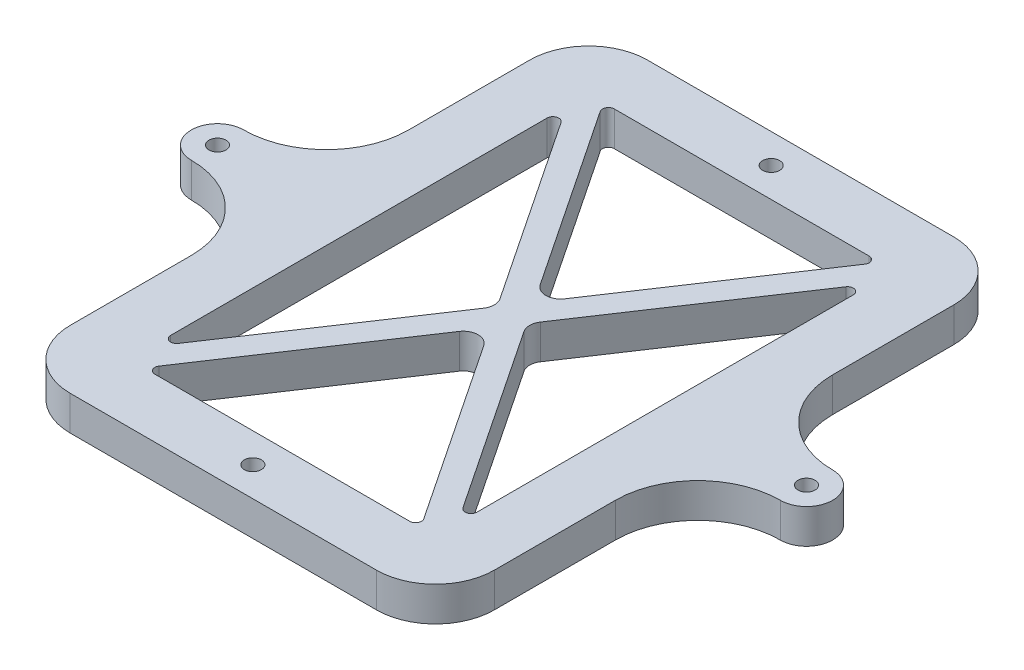
SolidWorks part; units mm, degrees
material "Acrylic (Medium-high impact)"
ref_plane "Front Plane" through (0, 0, 0) normal (0, 0, 1) x (1, 0, 0)
ref_plane "Top Plane" through (0, 0, 0) normal (0, 1, 0) x (1, 0, 0)
ref_plane "Right Plane" through (0, 0, 0) normal (1, 0, 0) x (0, 0, -1)
sketch "Sketch1" plane through (0, 0, 0) normal (0, 1, 0) x (1, 0, 0)
  line L0 (-36, 49) -> (-36, 18.45) construction
  line L1 (-36, 49) -> (36, 49) construction
  line L2 (-36, -49) -> (36, -49) construction
  line L3 (36, 49) -> (36, 18.45) construction
  line L4 (-28.5, -39) -> (-23.5, -39)
  line L5 (-28.5, -39) -> (23.5, 39)
  line L6 (-55, 0) -> (55, 0) construction
  line L7 (-74.55, 39) -> (-36, 39) construction
  line L8 (-26, 39) -> (26, 39)
  line L9 (-26, 39) -> (-26, -39)
  line L10 (-26, -39) -> (26, -39)
  line L11 (26, 39) -> (26, -39)
  line L12 (-26, 39) -> (26, -39) construction
  line L13 (-26, -39) -> (26, 39) construction
  line L14 (-71.5261, -39) -> (60.5097, -39) construction
  line L15 (-36, 39) -> (-36, 18.45)
  line L16 (-26, -996.6512) -> (-26, 49003.3488) construction
  line L17 (26, -1000) -> (26, 49000) construction
  line L18 (-26, 49) -> (26, 49)
  line L19 (36, 39) -> (36, 18.45)
  line L20 (-26, -49) -> (26, -49)
  line L21 (-62.4665, 0) -> (49937.5335, 0) construction
  line L22 (0, 0) -> (0, 50000) construction
  line L23 (-23.5, -39) -> (26, 35.25)
  line L24 (23.5, 39) -> (26, 39)
  line L25 (28.5, -39) -> (23.5, -39)
  line L26 (28.5, -39) -> (-23.5, 39)
  line L27 (23.5, -39) -> (-26, 35.25)
  line L28 (-23.5, 39) -> (-26, 39)
  line L29 (-36, -18.45) -> (-36, -49) construction
  line L30 (-36, -18.45) -> (-36, -39)
  line L31 (36, -18.45) -> (36, -49) construction
  line L32 (36, -18.45) -> (36, -39)
  line L33 (-26, 39) -> (26, 39) construction
  line L34 (36, 39) -> (60.5097, 39) construction
  arc A0 (-36, 39) -> (-26, 49) centre (-26, 39) cw
  arc A1 (26, 49) -> (36, 39) centre (26, 39) cw
  arc A2 (36, -39) -> (26, -49) centre (26, -39) cw
  arc A3 (-26, -49) -> (-36, -39) centre (-26, -39) cw
  circle A4 centre (0, 44) radius 1.45
  circle A5 centre (0, -44) radius 1.45
  circle A6 centre (-50, 0) radius 1.45
  circle A7 centre (50, 0) radius 1.45
  arc A8 (-50, -4.45) -> (-50, 4.45) centre (-50, 0) cw
  arc A9 (-50, 4.45) -> (-36, 18.45) centre (-50, 18.45) ccw
  arc A10 (-50, -4.45) -> (-36, -18.45) centre (-50, -18.45) cw
  arc A11 (50, -4.45) -> (50, 4.45) centre (50, 0) ccw
  arc A12 (50, -4.45) -> (36, -18.45) centre (50, -18.45) ccw
  arc A13 (50, 4.45) -> (36, 18.45) centre (50, 18.45) cw
  point P1 (0, 0)
  point P3 (0, 0)
  point P24 (26, 0)
  point P25 (36, 39)
  point P26 (36, -39)
  point P27 (-26, 49)
  point P28 (26, 49)
  point P34 (26, -49)
  point P35 (-26, -49)
  dimension "D7" = 2.9
  dimension "D8" = 2.5
  dimension "D10" = 50
  dimension "D11" = 2.9
  dimension "D5" = 44
  dimension "D9" = 3
  dimension "D1" = 98
  dimension "D2" = 72
  dimension "D3" = 78
  dimension "D4" = 52
extrude "Boss-Extrude1" add sketch "Sketch1" along normal blind 5.85 contours A3 L20 A2 L19 A1 L18 A0 L15 A7 A6 A5 A4 L28 L8 L24 L23 L11 L26 L25 L10 L4 L5 L9 L27 | L23 L27 L5 L9 L4 | L27 L5 L26 L8 L9 | L9 L28 L27 | L9 L5 L4 | L25 L26 L11 | L27 L10 L11 L26 L23 | L27 L23 L26 L5 | L26 L23 L11 L8 L5 | L24 L11 L23 region at (-26.8333, 0, 37.75) region at (-13.3152, 0, 19.9728) region at (-13.3152, 0, -19.9728) region at (0, 0, 0) region at (13.3152, 0, 19.9728) region at (13.3152, 0, -19.9728) region at (26.8333, 0, 37.75) region at (-32.0351, 0, -45.0351)
fillet "Fillet1" radius 1 8 edges at (-26, 2.925, 35.25) (-23.5, 2.925, 39) (23.5, 2.925, 39) (26, 2.925, 35.25) (26, 2.925, -35.25) (23.5, 2.925, -39) (-26, 2.925, -35.25) (-23.5, 2.925, -39)
fillet "Fillet2" radius 2.5 4 edges at (2.5, 2.925, 0) (0, 2.925, 3.75) (0, 2.925, -3.75) (-2.5, 2.925, 0)
